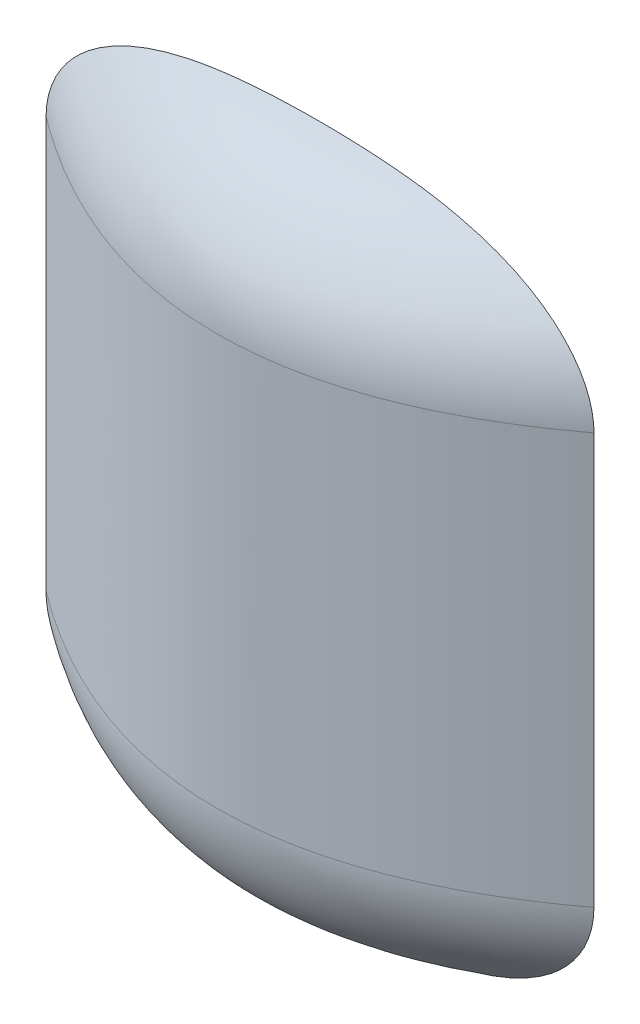
SolidWorks part; units mm, degrees
ref_plane "Front Plane" through (0, 0, 0) normal (0, 0, 1) x (1, 0, 0)
ref_plane "Top Plane" through (0, 0, 0) normal (0, 1, 0) x (1, 0, 0)
ref_plane "Right Plane" through (0, 0, 0) normal (1, 0, 0) x (0, 0, -1)
sketch "Sketch2" plane through (0, 0, 0) normal (0, 1, 0) x (1, 0, 0)
  line L0 (-50.7632, -14.8166) -> (50.8368, -14.8166)
  parabola Q0 (-50.7632, -14.8166) -> (50.8368, -14.8166) focus (0, 0) apex (-0.0235, -33.8666)
  dimension "D1" = 101.6
  dimension "D2" = 19.05
extrude "Boss-Extrude3" add sketch "Sketch2" along normal blind 127
fillet "Fillet2" radius 25.4 1 edges
fillet "Fillet3" radius 25.4 1 edges
shell "Shell3" thickness 3.175
